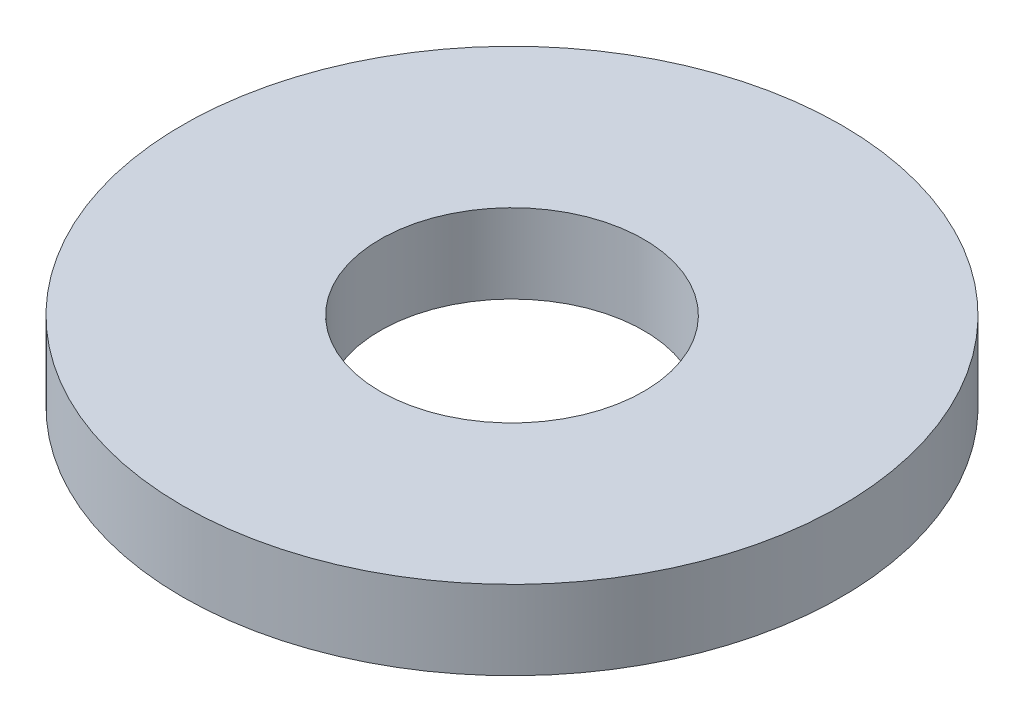
SolidWorks part; units mm, degrees
ref_plane "Front Plane" through (0, 0, 0) normal (0, 0, 1) x (1, 0, 0)
ref_plane "Top Plane" through (0, 0, 0) normal (0, 1, 0) x (1, 0, 0)
ref_plane "Right Plane" through (0, 0, 0) normal (1, 0, 0) x (0, 0, -1)
sketch "Sketch1" plane through (0, 0, 0) normal (0, 1, 0) x (1, 0, 0)
  circle A0 centre (0, 0) radius 62.5
  dimension "FLANGE_OD" = 125
extrude "Boss-Extrude1" add sketch "Sketch1" along normal blind 15
sketch "Sketch2" plane through (0, 0, 0) normal (0, 1, 0) x (1, 0, 0)
  circle A0 centre (0, 0) radius 25
  dimension "BORE_D" = 50
extrude "Cut-Extrude1" cut sketch "Sketch2" along normal through all
sketch "Sketch3" plane through (0, 15, 0) normal (0, 1, 0) x (1, 0, 0)
  circle A0 centre (0, 0) radius 20.2155 construction
  circle A1 centre (-20.2155, 0) radius 2.4211
  dimension "BOLT_D" = 4.8422
  dimension "BOLT_PCD" = 40.431
extrude "Cut-Extrude2" cut sketch "Sketch3" against normal blind 14.8187 rebuild error yes
pattern_circular "CirPattern1" count 5 over 360 rebuild error yes
